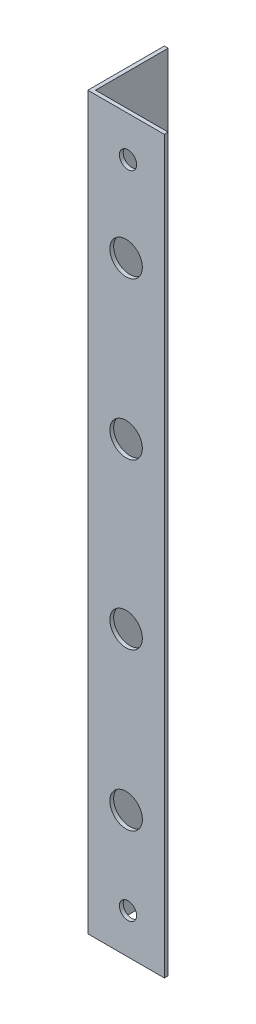
SolidWorks part; units mm, degrees
material "1060 Сплав"
ref_plane "Спереди" through (0, 0, 0) normal (0, 0, 1) x (1, 0, 0)
ref_plane "Сверху" through (0, 0, 0) normal (0, 1, 0) x (1, 0, 0)
ref_plane "Справа" through (0, 0, 0) normal (1, 0, 0) x (0, 0, -1)
sketch "Эскиз1" plane through (0, 0, 0) normal (0, 1, 0) x (1, 0, 0)
  line L0 (0, 0) -> (0, 20)
  line L1 (0, 20) -> (1, 20)
  line L2 (1, 20) -> (1, 1)
  line L3 (1, 1) -> (20, 1)
  line L4 (20, 1) -> (20, 0)
  line L5 (20, 0) -> (0, 0)
  dimension "D1" = 1
  dimension "D2" = 20
extrude "Бобышка-Вытянуть1" add sketch "Эскиз1" along normal blind 191
sketch "Эскиз2" plane through (0, 0, 0) normal (0, 0, 1) x (1, 0, 0)
  line L0 (10, 191) -> (10, 0) construction
  line L1 (0, 191) -> (20, 191) construction
  line L2 (0, 0) -> (20, 0) construction
  line L3 (20, 95.5) -> (0, 95.5) construction
  line L4 (20, 191) -> (20, 0) construction
  line L5 (0, 191) -> (0, 0) construction
  circle A0 centre (10, 158) radius 4.25
  circle A1 centre (10, 117) radius 4.25
  circle A2 centre (10, 74) radius 4.25
  circle A3 centre (10, 33) radius 4.25
  dimension "D1" = 8.5
  dimension "D2" = 8.5
  dimension "D3" = 8.5
  dimension "D4" = 8.5
  dimension "D6" = 41
  dimension "D7" = 41
  dimension "D8" = 33
  dimension "D9" = 43
  dimension "D5" = 33
extrude "Вырез-Вытянуть1" cut sketch "Эскиз2" against normal through all
sketch "Эскиз3" plane through (0, 0, -1) normal (0, 0, -1) x (-1, 0, 0)
  circle A0 centre (-10.5, 10.5) radius 2.25 construction
  circle A1 centre (-10.5, 10.5) radius 2.25
  circle A2 centre (-10.5, 180.5) radius 2.25 construction
  circle A3 centre (-10.5, 180.5) radius 2.25
extrude "Вырез-Вытянуть2" cut sketch "Эскиз3" against normal through all
